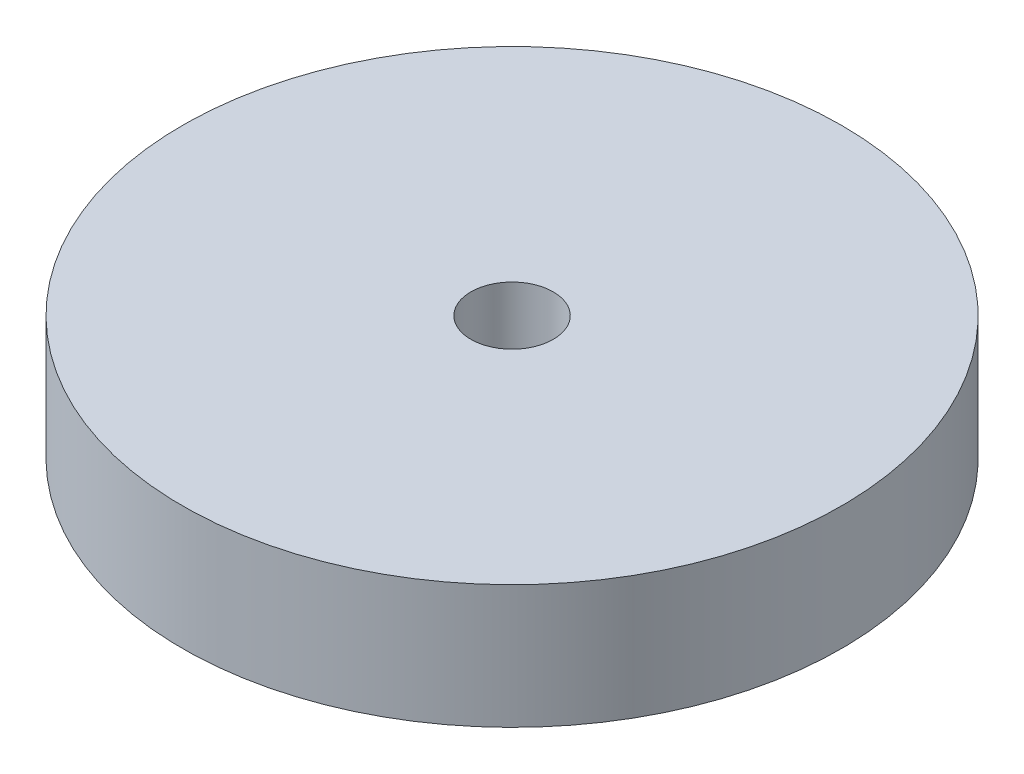
SolidWorks part; units mm, degrees
ref_plane "Front Plane" through (0, 0, 0) normal (0, 0, 1) x (1, 0, 0)
ref_plane "Top Plane" through (0, 0, 0) normal (0, 1, 0) x (1, 0, 0)
ref_plane "Right Plane" through (0, 0, 0) normal (1, 0, 0) x (0, 0, -1)
sketch "Sketch1" plane through (0, 0, 0) normal (0, 1, 0) x (1, 0, 0)
  circle A0 centre (0, 0) radius 25.4
  circle A1 centre (0, 0) radius 3.175
  dimension "D1" = 50.8
  dimension "D2" = 6.35
extrude "Boss-Extrude1" add sketch "Sketch1" along normal blind 9.525
